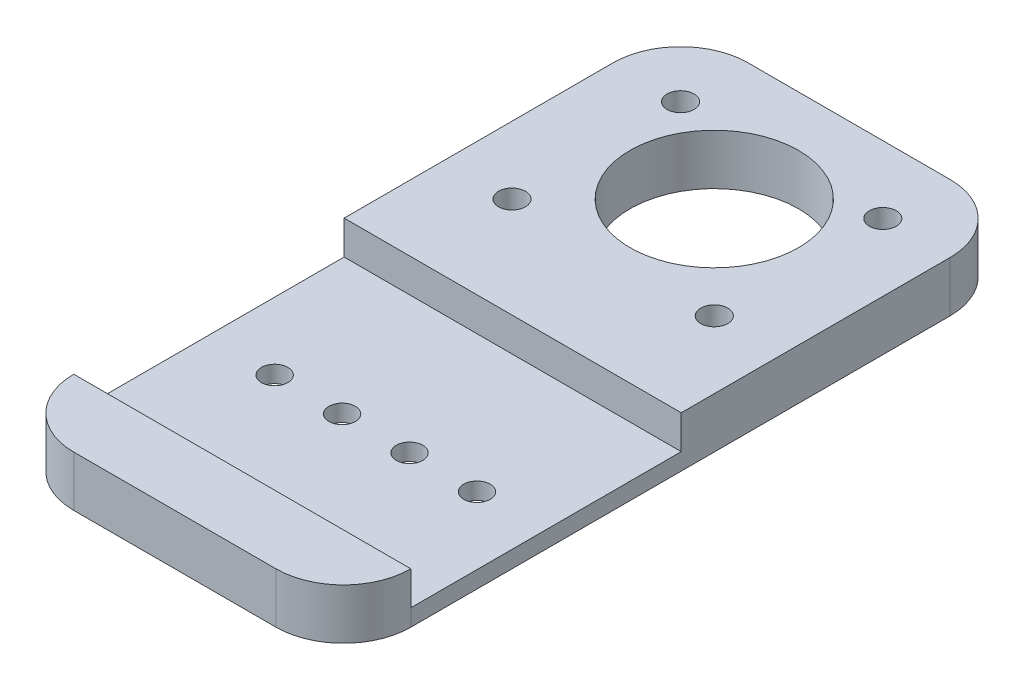
SolidWorks part; units mm, degrees
ref_plane "Front Plane" through (0, 0, 0) normal (0, 0, 1) x (1, 0, 0)
ref_plane "Top Plane" through (0, 0, 0) normal (0, 1, 0) x (1, 0, 0)
ref_plane "Right Plane" through (0, 0, 0) normal (1, 0, 0) x (0, 0, -1)
sketch "Sketch1" plane through (0, 0, 0) normal (0, 1, 0) x (1, 0, 0)
  line L0 (0, -111.3091) -> (63.5, -111.3091)
  line L1 (0, 2.9909) -> (63.5, 2.9909)
  line L2 (0, 2.9909) -> (0, -124.0091)
  line L3 (0, -124.0091) -> (63.5, -124.0091)
  line L4 (63.5, 2.9909) -> (63.5, -124.0091)
  line L7 (0, -60.3821) -> (63.5, -60.3821)
  circle A0 centre (31.75, -22.4091) radius 15.875
  circle A1 centre (12.7, -86.1631) radius 2.4892
  circle A2 centre (25.4, -86.1631) radius 2.4892
  circle A3 centre (38.1, -86.1631) radius 2.4892
  circle A4 centre (50.8, -86.1631) radius 2.4892
  dimension "D3" = 31.75
  dimension "D4" = 25.4
  dimension "D5" = 31.75
  dimension "D6" = 4.9784
  dimension "D7" = 12.7
  dimension "D8" = 37.846
  dimension "D1" = 63.5
  dimension "D2" = 127
  dimension "D10" = 12.7
  dimension "D12" = 63.627
  dimension "D9" = 4
extrude "Boss-Extrude2" add sketch "Sketch1" along normal blind 9.525 contours L4 L0 L2 L3 | L2 L7 L4 L1 A0 region at (31.75, 0, 117.6591) region at (0.8971, 0, 28.6956)
extrude "Boss-Extrude3" add sketch "Sketch1<3>" along normal blind 3.175 contours L7 L2 L0 L4 A4 A3 A2 A1 region at (31.75, 0, 85.8377)
sketch "Sketch1<3>" plane through (0, 0, 0) normal (0, 1, 0) x (1, 0, 0) same geometry as "Sketch1"
fillet "Fillet2" radius 12.7 4 edges at (0, 4.7625, 124.0091) (63.5, 4.7625, 124.0091) (0, 4.7625, -2.9909) (63.5, 4.7625, -2.9909)
sketch "Sketch2" plane through (0, 0, 0) normal (0, -1, 0) x (1, 0, 0)
  circle A0 centre (12.7, 41.4591) radius 2.54
  circle A1 centre (50.8, 41.4591) radius 2.54
  circle A2 centre (50.8, 9.7091) radius 2.54
  circle A3 centre (12.7, 9.7091) radius 2.54
  arc A8 (0, 9.7091) -> (12.7, -2.9909) centre (12.7, 9.7091) ccw construction
  arc A9 (50.8, -2.9909) -> (63.5, 9.7091) centre (50.8, 9.7091) ccw construction
  point P11 (49.0118, 109.8708)
  point P14 (0, 0)
  point P15 (0, 0)
  point P16 (0, 0)
  point P17 (0, 0)
  point P18 (12.7, 49.9513)
  point P20 (0, 0)
  dimension "D1" = 5.08
  dimension "D2" = 31.75
extrude "Cut-Extrude1" cut sketch "Sketch2" against normal through all
